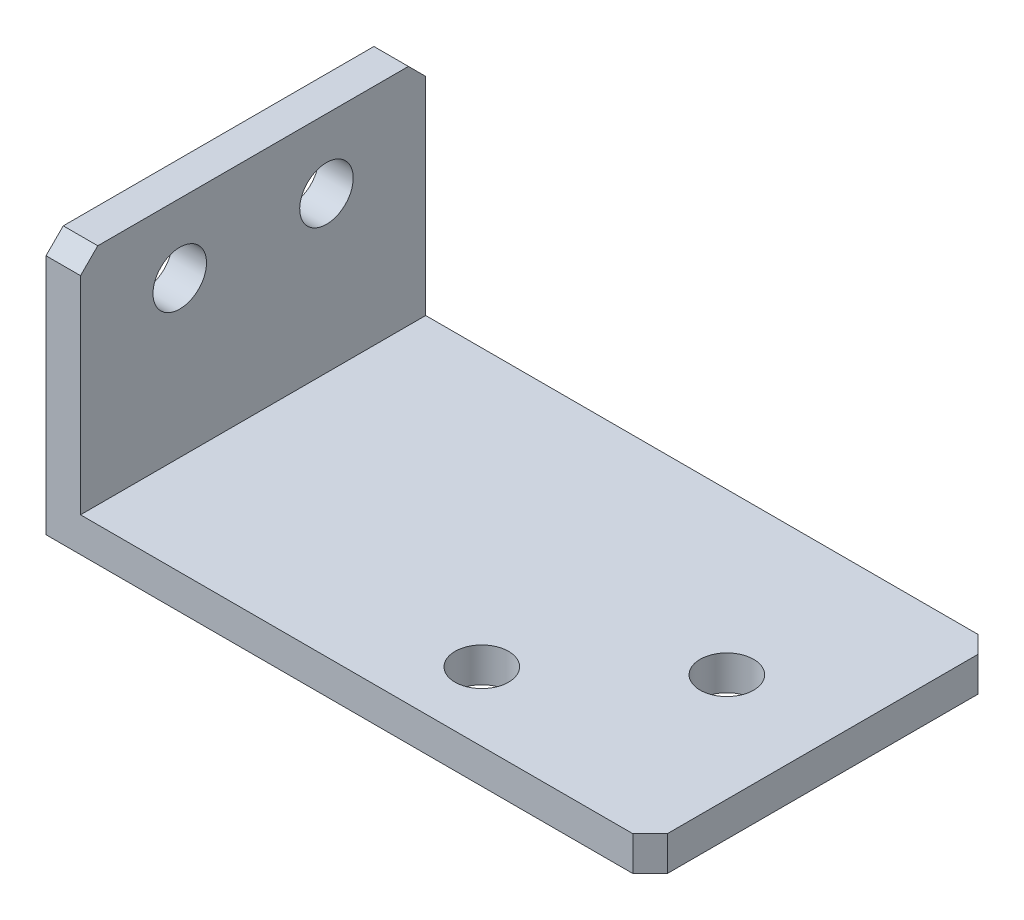
SolidWorks part; units mm, degrees
material "6063-T5"
ref_plane "Спереди" through (0, 0, 0) normal (0, 0, 1) x (1, 0, 0)
ref_plane "Сверху" through (0, 0, 0) normal (0, 1, 0) x (1, 0, 0)
ref_plane "Справа" through (0, 0, 0) normal (1, 0, 0) x (0, 0, -1)
sketch "Sketch1" plane through (0, 0, 0) normal (0, 0, 1) x (1, 0, 0)
  line L0 (0, 0) -> (35, 0)
  line L1 (35, 0) -> (35, 2)
  line L2 (35, 2) -> (2, 2)
  line L3 (2, 2) -> (2, 15)
  line L4 (2, 15) -> (0, 15)
  line L5 (0, 15) -> (0, 0)
  point P3 (0, 0)
  dimension "D1" = 35
  dimension "D2" = 15
  dimension "D4" = 2
extrude "Base" add sketch "Sketch1" along normal blind 20
sketch "Sketch2" plane through (0, 0, 0) normal (-1, 0, 0) x (0, 0, 1)
  line L2 (20, 0) -> (0, 0) construction
  line L3 (10, 0) -> (10, 14.2922) construction
  circle A0 centre (14.25, 11) radius 1.55
  circle A1 centre (5.75, 11) radius 1.55
  dimension "D5" = 3.1
  dimension "D1" = 8.5
  dimension "D3" = 11
extrude "CarriageSide" cut sketch "Sketch2" against normal up to surface (2 mm away) up to face at (2, 8.5, 10)
sketch "Sketch5" plane through (0, 2, 0) normal (0, 1, 0) x (1, 0, 0)
  line L0 (0, -20) -> (0, 0) construction
  line L2 (35, -20) -> (2, -20) construction
  circle A0 centre (21.25, -16) radius 1.55
  circle A1 centre (28.75, -9.3) radius 1.55
  dimension "D3" = 3.1
  dimension "D1" = 4
  dimension "D2" = 6.7
  dimension "D4" = 7.5
  dimension "D5" = 21.25
extrude "CableChainSide" cut sketch "Sketch5" against normal through all
chamfer "Chamfer1" distance 1 angle 45 4 edges at (35, 1, 0) (1, 15, 0) (1, 15, 20) (35, 1, 20)
